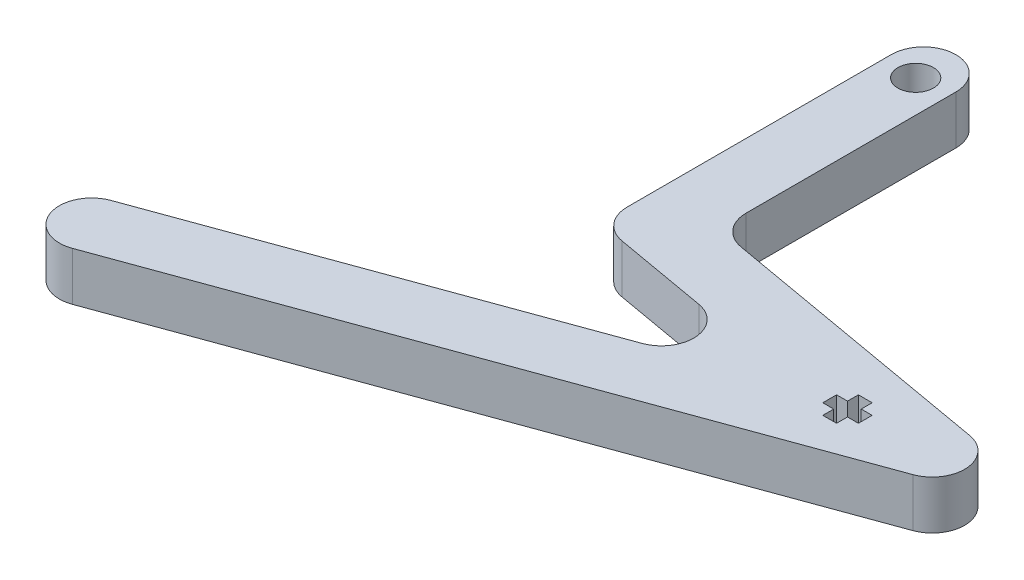
SolidWorks part; units mm, degrees
ref_plane "Front Plane" through (0, 0, 0) normal (0, 0, 1) x (1, 0, 0)
ref_plane "Top Plane" through (0, 0, 0) normal (0, 1, 0) x (1, 0, 0)
ref_plane "Right Plane" through (0, 0, 0) normal (1, 0, 0) x (0, 0, -1)
sketch "Sketch1" plane through (0, 0, 0) normal (0, 1, 0) x (1, 0, 0)
  line L16 (-71.479, 49.0484) -> (-71.479, 9.0484)
  line L19 (-63.479, 15.7612) -> (-63.479, 49.0484)
  line L22 (-63.479, 15.7612) -> (-11.1428, 6.533)
  line L26 (-71.479, 9.0484) -> (-41.9348, 3.839)
  line L27 (-41.9348, 3.839) -> (-107.8482, -20.1515)
  line L28 (-107.8482, -20.1515) -> (-105.1121, -27.6691)
  line L29 (-105.1121, -27.6691) -> (-11.1428, 6.533)
  line L30 (-71.479, 49.0484) -> (-63.479, 49.0484)
  line L43 (-38.433, 5.2517) -> (-38.433, 3.5517)
  line L44 (-38.433, 3.5517) -> (-37.083, 3.5517)
  line L45 (-37.083, 3.5517) -> (-37.083, 2.2017)
  line L46 (-37.083, 2.2017) -> (-35.383, 2.2017)
  line L47 (-35.383, 2.2017) -> (-35.383, 3.5517)
  line L48 (-35.383, 3.5517) -> (-34.033, 3.5517)
  line L49 (-34.033, 3.5517) -> (-34.033, 5.2517)
  line L50 (-34.033, 5.2517) -> (-35.383, 5.2517)
  line L51 (-35.383, 5.2517) -> (-35.383, 6.6017)
  line L52 (-35.383, 6.6017) -> (-37.083, 6.6017)
  line L53 (-37.083, 6.6017) -> (-37.083, 5.2517)
  line L54 (-37.083, 5.2517) -> (-38.433, 5.2517)
  circle A46 centre (-67.479, 44.0775) radius 2.2
  circle A47 centre (-36.233, 4.4017) radius 2.3585 construction
  point P44 (-67.479, 49.0484)
  dimension "D2" = 1.7
  dimension "D3" = 8
  dimension "D1" = 1.35
  dimension "D8" = 4.4
  dimension "D4" = 100
  dimension "D5" = 30
  dimension "D6" = 8
  dimension "D7" = 8
  dimension "D10" = 40
  dimension "D11" = 100
  dimension "D12" = 30
extrude "Boss-Extrude1" add sketch "Sketch1" along normal blind 6
fillet "Fillet1" radius 4 8 edges at (-63.479, 3, -15.7612) (-71.479, 3, -9.0484) (-105.1121, 3, 27.6691) (-107.8482, 3, 20.1515) (-41.9348, 3, -3.839) (-11.1428, 3, -6.533) (-63.479, 3, -49.0484) (-71.479, 3, -49.0484)
sketch "Sketch2" plane through (0, 6, 0) normal (0, 1, 0) x (1, 0, 0)
  line L6 (-71.479, 45.0484) -> (-71.479, 12.4048)
  line L7 (-68.1736, 8.4656) -> (-56.6362, 6.4313)
  line L8 (-55.9627, -1.2667) -> (-104.0895, -18.7834)
  line L9 (-101.3533, -26.301) -> (-25.1707, 1.4272)
  line L10 (-25.8442, 9.1252) -> (-60.1736, 15.1784)
  line L11 (-63.479, 19.1176) -> (-63.479, 45.0484)
  line L12 (-38.433, 5.2517) -> (-38.433, 3.5517)
  line L13 (-37.083, 5.2517) -> (-38.433, 5.2517)
  line L14 (-37.083, 6.6017) -> (-37.083, 5.2517)
  line L15 (-35.383, 6.6017) -> (-37.083, 6.6017)
  line L16 (-35.383, 5.2517) -> (-35.383, 6.6017)
  line L17 (-34.033, 5.2517) -> (-35.383, 5.2517)
  line L18 (-34.033, 3.5517) -> (-34.033, 5.2517)
  line L19 (-35.383, 3.5517) -> (-34.033, 3.5517)
  line L20 (-35.383, 2.2017) -> (-35.383, 3.5517)
  line L21 (-37.083, 2.2017) -> (-35.383, 2.2017)
  line L22 (-37.083, 3.5517) -> (-37.083, 2.2017)
  line L23 (-38.433, 3.5517) -> (-37.083, 3.5517)
  line L24 (-38.433, 5.2517) -> (-38.433, 3.5517)
  line L25 (-37.083, 5.2517) -> (-38.433, 5.2517)
  line L26 (-37.083, 6.6017) -> (-37.083, 5.2517)
  line L27 (-35.383, 6.6017) -> (-37.083, 6.6017)
  line L28 (-35.383, 5.2517) -> (-35.383, 6.6017)
  line L29 (-34.033, 5.2517) -> (-35.383, 5.2517)
  line L30 (-34.033, 3.5517) -> (-34.033, 5.2517)
  line L31 (-35.383, 3.5517) -> (-34.033, 3.5517)
  line L32 (-35.383, 2.2017) -> (-35.383, 3.5517)
  line L33 (-37.083, 2.2017) -> (-35.383, 2.2017)
  line L34 (-37.083, 3.5517) -> (-37.083, 2.2017)
  line L35 (-38.433, 3.5517) -> (-37.083, 3.5517)
  line L36 (-71.479, 45.0484) -> (-71.479, 12.4048)
  line L37 (-68.1736, 8.4656) -> (-56.6362, 6.4313)
  line L38 (-55.9627, -1.2667) -> (-104.0895, -18.7834)
  line L39 (-101.3533, -26.301) -> (-25.1707, 1.4272)
  line L40 (-25.8442, 9.1252) -> (-60.1736, 15.1784)
  line L41 (-63.479, 19.1176) -> (-63.479, 45.0484)
  circle A1 centre (-67.479, 44.0775) radius 2.2
  circle A2 centre (-67.479, 44.0775) radius 2.2
  arc A10 (-71.479, 12.4048) -> (-68.1736, 8.4656) centre (-67.479, 12.4048) ccw
  arc A11 (-55.9627, -1.2667) -> (-56.6362, 6.4313) centre (-57.3308, 2.492) ccw
  arc A12 (-104.0895, -18.7834) -> (-106.4801, -23.9103) centre (-102.7214, -22.5422) ccw
  arc A13 (-106.4801, -23.9103) -> (-101.3533, -26.301) centre (-102.7214, -22.5422) ccw
  arc A14 (-25.1707, 1.4272) -> (-25.8442, 9.1252) centre (-26.5388, 5.186) ccw
  arc A15 (-63.479, 19.1176) -> (-60.1736, 15.1784) centre (-59.479, 19.1176) ccw
  arc A16 (-63.479, 45.0484) -> (-67.479, 49.0484) centre (-67.479, 45.0484) ccw
  arc A17 (-67.479, 49.0484) -> (-71.479, 45.0484) centre (-67.479, 45.0484) ccw
  arc A18 (-71.479, 12.4048) -> (-68.1736, 8.4656) centre (-67.479, 12.4048) ccw
  arc A19 (-55.9627, -1.2667) -> (-56.6362, 6.4313) centre (-57.3308, 2.492) ccw
  arc A20 (-104.0895, -18.7834) -> (-106.4801, -23.9103) centre (-102.7214, -22.5422) ccw
  arc A21 (-106.4801, -23.9103) -> (-101.3533, -26.301) centre (-102.7214, -22.5422) ccw
  arc A22 (-25.1707, 1.4272) -> (-25.8442, 9.1252) centre (-26.5388, 5.186) ccw
  arc A23 (-63.479, 19.1176) -> (-60.1736, 15.1784) centre (-59.479, 19.1176) ccw
  arc A24 (-63.479, 45.0484) -> (-67.479, 49.0484) centre (-67.479, 45.0484) ccw
  arc A25 (-67.479, 49.0484) -> (-71.479, 45.0484) centre (-67.479, 45.0484) ccw
  dimension "D1" = 0
  dimension "D2" = 0
  dimension "D3" = 0
